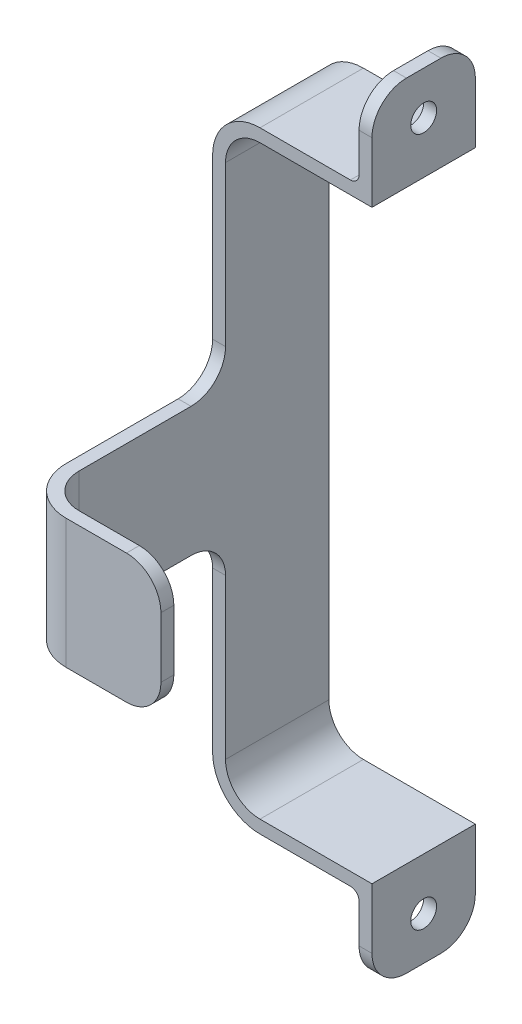
SolidWorks part; units mm, degrees
material "ABS"
ref_plane "Plan de face" through (0, 0, 0) normal (0, 0, 1) x (1, 0, 0)
ref_plane "Plan de dessus" through (0, 0, 0) normal (0, 1, 0) x (1, 0, 0)
ref_plane "Plan de droite" through (0, 0, 0) normal (1, 0, 0) x (0, 0, -1)
sketch "Esquisse1" plane through (0, 0, 0) normal (0, 0, 1) x (1, 0, 0)
  line L0 (0, 34) -> (0, 45)
  line L1 (0, 34) -> (-13, 34)
  line L2 (0, 34) -> (0, -34) construction
  line L3 (0, -34) -> (-13, -34)
  line L4 (-17, 30) -> (-17, -30)
  line L5 (0, -34) -> (0, -45)
  arc A0 (-13, -34) -> (-17, -30) centre (-13, -30) cw
  arc A1 (-13, 34) -> (-17, 30) centre (-13, 30) ccw
  dimension "D1" = 4
  dimension "D2" = 68
  dimension "D3" = 17
  dimension "D4" = 11
  dimension "D5" = 90
extrude "Extru.-Mince1" add sketch "Esquisse1" along normal mid plane 12 thin thin type one direction wall 1.5
sketch "Esquisse2" plane through (0, 0, 0) normal (0, 1, 0) x (1, 0, 0)
  line L0 (-17, -6) -> (-17, -23)
  line L1 (-13, -27) -> (-2, -27)
  arc A0 (-17, -23) -> (-13, -27) centre (-13, -23) ccw
  dimension "D1" = 15
  dimension "D2" = 4
  dimension "D3" = 21
extrude "Extru.-Mince2" add sketch "Esquisse2" along normal mid plane 15 thin thin type one direction wall 1.5
fillet "Congé1" radius 4 8 edges at (-0.75, 45, -6) (-0.75, 45, 6) (-2, 7.5, 27.75) (-2, -7.5, 27.75) (-0.75, -45, -6) (-0.75, -45, 6)
fillet "Congé2" radius 1 2 edges at (-1.5, 35.5, 0) (-1.5, -35.5, 0)
sketch "Esquisse3" plane through (0, 0, 0) normal (1, 0, 0) x (0, 0, -1)
  line L0 (6, 0) -> (0, 0) construction
  line L1 (6, 30) -> (6, -30) construction
  line L2 (-2, 45) -> (2, 45) construction
  circle A0 centre (0, 40) radius 1.5
  circle A1 centre (0, -40) radius 1.5
  dimension "D1" = 3
  dimension "D2" = 5
extrude "Enlèv. mat.-Extru.1" cut sketch "Esquisse3" against normal through all
